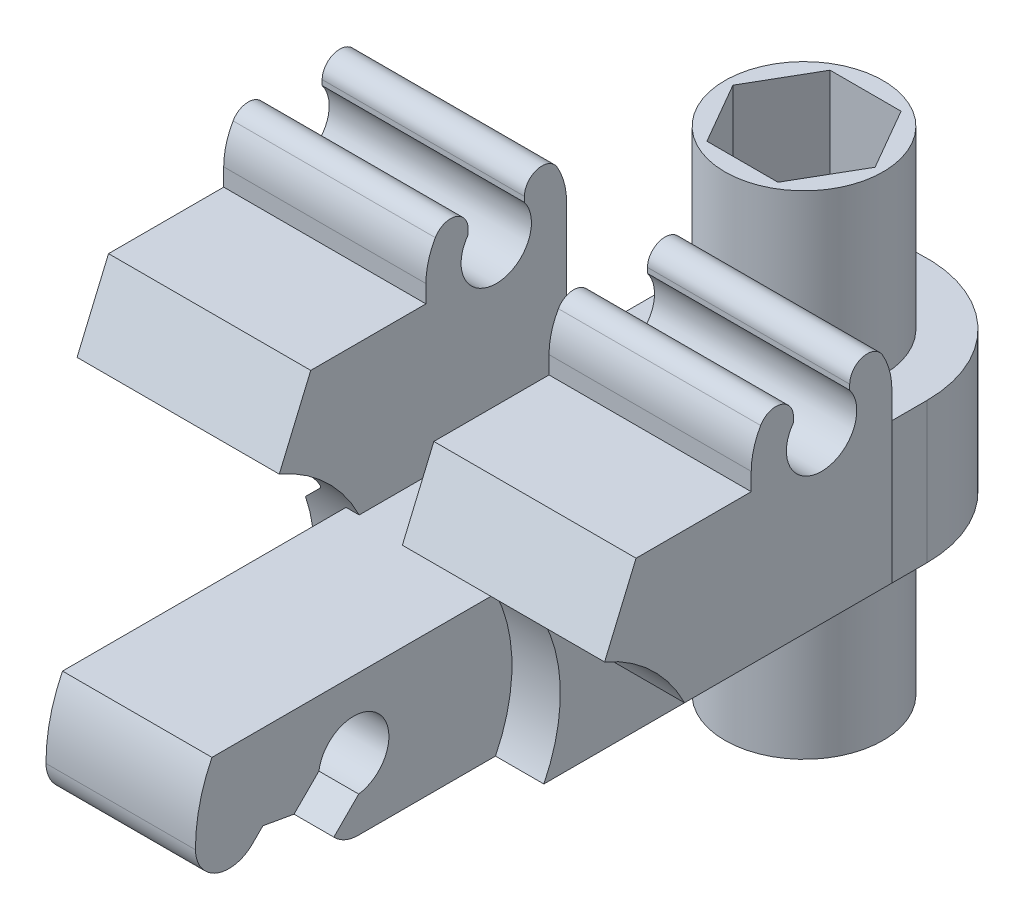
SolidWorks part; units mm, degrees
ref_plane "Front Plane" through (0, 0, 0) normal (0, 0, 1) x (1, 0, 0)
ref_plane "Top Plane" through (0, 0, 0) normal (0, 1, 0) x (1, 0, 0)
ref_plane "Right Plane" through (0, 0, 0) normal (1, 0, 0) x (0, 0, -1)
sketch "Sketch3" plane through (0, 0, 0) normal (1, 0, 0) x (0, 0, -1)
  line L0 (0.2828, -1.9799) -> (-1.9799, 0.2828)
  line L1 (0.2828, -1.9799) -> (-1.1314, -3.3941)
  line L2 (-1.1314, -3.3941) -> (-0.8188, -5.1668)
  line L3 (-0.8188, -5.1668) -> (-3.8071, -8.1551)
  line L4 (-1.9799, 0.2828) -> (-3.3941, -1.1314)
  line L5 (-3.3941, -1.1314) -> (-5.1668, -0.8188)
  line L6 (-5.1668, -0.8188) -> (-8.1551, -3.8071)
  line L7 (-0.8485, -0.8485) -> (0, 0) construction
  line L8 (0, 0) -> (-2, 0) construction
  line L9 (-1.9799, 0.2828) -> (-5.1668, -0.8188) construction
  line L10 (-0.8188, -5.1668) -> (0.2828, -1.9799) construction
  circle A0 centre (0, 0) radius 2
  circle A1 centre (0, 0) radius 8.5 construction
  circle A2 centre (0, 0) radius 9 construction
  circle A3 centre (0, 0) radius 9
  dimension "D1" = 4
  dimension "D2" = 17
  dimension "D3" = 7
  dimension "D4" = 0.5
  dimension "D5" = 2
  dimension "D7" = 3.2
  dimension "D6" = 1.8
  dimension "D8" = 45
  dimension "D9" = 125
extrude "Boss-Extrude1" add sketch "Sketch3" along normal mid plane 8.5 contours A3 L6 L5 L4 A0 L1 L2 L3 | A3 region at (0, -1.4772, -1.7032)
sketch "Sketch5" plane through (0, 0, 0) normal (1, 0, 0) x (0, 0, -1)
  line L0 (0, 9) -> (29.856, 9)
  line L1 (29.856, 9) -> (29.856, -9)
  line L2 (29.856, -9) -> (0, -9)
  arc A0 (-3.8071, -8.1551) -> (-8.1551, -3.8071) centre (0, 0) ccw construction
  arc A1 (0, -9) -> (0, 9) centre (0, 0) ccw
  dimension "D1" = 29.856
extrude "Boss-Extrude2" add sketch "Sketch5" along normal mid plane 14
sketch "Sketch6" plane through (0, 9, 0) normal (0, 1, 0) x (1, 0, 0)
  line L0 (7, 29.856) -> (-7, 29.856) construction
  circle A0 centre (0, 29.856) radius 7
extrude "Boss-Extrude3" add sketch "Sketch6" against normal up to surface (18 mm away) up to face at (0, -9, -9.952)
sketch "Sketch7" plane through (0, 0, 0) normal (0, 1, 0) x (1, 0, 0)
  circle A0 centre (0, 29.856) radius 4.5
  dimension "D1" = 9
extrude "Boss-Extrude4" add sketch "Sketch7" along normal blind 14 and the other way blind 14
sketch "Sketch22" plane through (0, 14, 0) normal (0, 1, 0) x (1, 0, 0)
  circle A0 centre (0, 29.856) radius 3
  dimension "D1" = 6
extrude "Boss-Extrude6" [suppressed] add sketch "Sketch22" along normal blind 18
sketch "Sketch8" plane through (0, 9, 0) normal (0, 1, 0) x (1, 0, 0)
  line L0 (4.25, -9) -> (4.25, 0) construction
  line L1 (-4.25, 0) -> (-4.25, -9) construction
  line L3 (7, 0) -> (7, 29.856) construction
  line L4 (-7, 29.856) -> (-7, 0) construction
  line L5 (-7, 0) -> (-4.25, 0) construction
  line L6 (4.25, 0) -> (7, 0) construction
  line L7 (4.25, -9) -> (4.25, 0)
  line L8 (-4.25, 0) -> (-4.25, -9)
  line L9 (-4.25, -9) -> (4.25, -9)
  line L10 (7, 0) -> (7, 29.856)
  line L11 (-7, 29.856) -> (-7, 0)
  line L12 (-7, 0) -> (-4.25, 0)
  line L13 (4.25, 0) -> (7, 0)
  arc A0 (7, 29.856) -> (-7, 29.856) centre (0, 29.856) ccw construction
  arc A1 (7, 29.856) -> (-7, 29.856) centre (0, 29.856) ccw
  circle M9 centre (0, 29.856) radius 4.5
  line M10 (7, 0) -> (7, 29.856)
  arc M11 (7, 29.856) -> (-7, 29.856) centre (0, 29.856) ccw
  line M12 (-7, 29.856) -> (-7, 0)
  line M13 (-7, 0) -> (-4.25, 0)
  line M14 (-4.25, 0) -> (4.25, 0)
  line M15 (4.25, 0) -> (7, 0)
extrude "Cut-Extrude2" cut sketch "Sketch8" against normal offset from surface (5 mm away) 4 contours M15 M10 M11 M12 M13 M14 M9 | L8 L9 L7 M14 region at (0, 9, 4.5) region at (0, 9, -15.9202) up to plane "Top Plane"
sketch "Sketch9" plane through (0, -9, 0) normal (0, -1, 0) x (1, 0, 0)
  line L7 (4.25, 0) -> (4.25, 9)
  line L8 (7, 0) -> (4.25, 0)
  line L9 (7, -29.856) -> (7, 0)
  line L10 (-7, 0) -> (-7, -29.856)
  line L11 (-4.25, 0) -> (-7, 0)
  line L12 (-4.25, 9) -> (-4.25, 0)
  line L13 (4.25, 9) -> (-4.25, 9)
  line L14 (4.25, 0) -> (4.25, 9)
  line L15 (7, 0) -> (4.25, 0)
  line L16 (7, -29.856) -> (7, 0)
  line L17 (-7, 0) -> (-7, -29.856)
  line L18 (-4.25, 0) -> (-7, 0)
  line L19 (-4.25, 9) -> (-4.25, 0)
  line L20 (4.25, 9) -> (-4.25, 9)
  arc A1 (-7, -29.856) -> (7, -29.856) centre (0, -29.856) ccw
  arc A2 (-7, -29.856) -> (7, -29.856) centre (0, -29.856) ccw
  circle M9 centre (0, -29.856) radius 4.5
  line M10 (-7, 0) -> (-7, -29.856)
  arc M11 (-7, -29.856) -> (7, -29.856) centre (0, -29.856) ccw
  line M12 (7, -29.856) -> (7, 0)
  line M13 (7, 0) -> (4.25, 0)
  line M14 (4.25, 0) -> (-4.25, 0)
  line M15 (-4.25, 0) -> (-7, 0)
  dimension "D1" = 0
extrude "Cut-Extrude4" cut sketch "Sketch9" against normal offset from surface (5 mm away) 4 contours M15 M10 M11 M12 M13 M14 M9 | L14 L20 L19 M14 region at (0, -9, 4.5) region at (0, -9, -15.9202) up to plane "Top Plane"
sketch "Sketch10" plane through (0, 0, 0) normal (1, 0, 0) x (0, 0, -1)
  line L3 (8.0623, -4) -> (29.856, -4)
  line L4 (29.856, -4) -> (29.856, 4)
  line L5 (29.856, 4) -> (8.0623, 4)
  line L10 (11.856, 12.5) -> (11.856, 17.5) construction
  line L11 (11.856, 17.5) -> (19.856, 17.5) construction
  line L12 (19.856, 17.5) -> (19.856, 4) construction
  line L13 (5.3059, 12.5) -> (11.856, 12.5)
  line L14 (0, 0) -> (3.5166, 8.2845) construction
  line L15 (3.5166, 8.2845) -> (5.3059, 12.5)
  line L16 (29.856, 4) -> (8.0623, 4) construction
  line L17 (19.856, 4) -> (8.0623, 4)
  line L18 (11.856, 13.5) -> (19.856, 13.5) construction
  line L19 (29.856, 14) -> (29.856, 4) construction
  line L20 (34.356, 14) -> (25.356, 14) construction
  line L21 (14.256, 14.7) -> (17.456, 14.7) construction
  line L22 (17.456, 14.7) -> (17.456, 17.1661)
  line L23 (14.256, 17.1661) -> (14.256, 14.7)
  line L24 (11.856, 13.5) -> (11.856, 12.5)
  line L25 (19.856, 13.5) -> (19.856, 4)
  arc A0 (14.256, 14.7) -> (17.456, 14.7) centre (15.856, 13.5) ccw
  arc A1 (8.0623, -4) -> (8.0623, 4) centre (0, 0) ccw
  arc A2 (8.0623, 4) -> (3.5166, 8.2845) centre (0, 0) ccw
  arc A3 (19.856, 13.5) -> (17.456, 17.1661) centre (15.856, 13.5) ccw
  arc A4 (14.256, 17.1661) -> (11.856, 13.5) centre (15.856, 13.5) ccw
  dimension "D8" = 4
  dimension "D9" = 2
  dimension "D10" = 3.2
  dimension "D2" = 67
  dimension "D3" = 10
  dimension "D4" = 13.5
  dimension "D5" = 5
  dimension "D7" = 5
  dimension "D1" = 0
extrude "Boss-Extrude5" add sketch "Sketch10" along normal mid plane 30
ref_plane "Plane1" through (6, 0, 0) normal (1, 0, 0) x (0, 0, -1)
ref_plane "Plane2" through (-6, 0, 0) normal (1, 0, 0) x (0, 0, -1)
sketch "Sketch13" plane through (-6, 0, 0) normal (1, 0, 0) x (0, 0, -1)
  line L0 (0, 5) -> (34.356, 5)
  line L1 (34.356, 4) -> (34.356, 14) construction
  circle A0 centre (0, 0) radius 5 construction
  dimension "D1" = 10
ref_plane "Plane3" through (0, 0, 0) normal (0, 0, 1) x (1, 0, 0)
sketch "Sketch14" plane through (0, 0, 0) normal (0, 0, 1) x (1, 0, 0)
  line L0 (-6.5303, 5.5303) -> (-8.0607, 4)
  line L1 (-7, 4) -> (-15, 4) construction
  line L2 (-5.4697, 4.4697) -> (-7, 2.9393)
  line L3 (-7, 4) -> (-7, -4) construction
  line L4 (-6.5303, 5.5303) -> (-5.4697, 4.4697) construction
  line L5 (-8.0607, 4) -> (-7, 4)
  line L6 (-7, 4) -> (-7, 2.9393)
  arc A0 (-5.4697, 4.4697) -> (-6.5303, 5.5303) centre (-6, 5) ccw
  point P14 (-6, 5)
  dimension "D1" = 1.5
  dimension "D2" = 45
sweep "Cut-Sweep1" cut profiles "Sketch14" path "Sketch13"
ref_plane "Plane4" [suppressed] through (0, 0, -32.856) normal (0, 0, -1) x (-1, 0, 0)
ref_plane "Plane5" [suppressed] through (-3, 0, 0) normal (-1, 0, 0) x (0, 0, 1)
sketch "Sketch18" [suppressed] plane through (0, 0, -32.856) normal (0, 0, -1) x (-1, 0, 0)
  line L0 (0, 29) -> (0, 16) construction
  line L2 (3, 29) -> (-3, 29) construction
  circle A0 centre (0, 16) radius 1.9
  dimension "D2" = 3.8
  dimension "D1" = 13
extrude "Cut-Extrude5" [suppressed] cut sketch "Sketch18" against normal blind 1
sketch "Sketch20" plane through (0, 14, 0) normal (0, 1, 0) x (1, 0, 0)
  line L0 (0, 25.356) -> (0, 0) construction
  line L2 (-3.5, -19.856) -> (3.5, -19.856)
  line L3 (-3.5, -19.856) -> (-3.5, 19.856)
  line L4 (-3.5, 19.856) -> (3.5, 19.856)
  line L5 (3.5, -19.856) -> (3.5, 19.856)
  line L6 (-3.5, -19.856) -> (3.5, 19.856) construction
  line L7 (-3.5, 19.856) -> (3.5, -19.856) construction
  line L8 (-5.9393, 19.856) -> (7, 19.856) construction
  circle A0 centre (0, 29.856) radius 4.5 construction
  circle A1 centre (0, 29.856) radius 4.5 construction
  dimension "D1" = 7
extrude "Cut-Extrude7" cut sketch "Sketch20" against normal up to surface (10 mm away) and the other way through all up to face at (0, 4, 0)
fillet "Fillet1" radius 1.9 2 edges at (0, -3.8071, 8.1551) (0, -4, 1.0245)
fillet "Fillet2" radius 1 4 edges at (-9.25, 17.1661, -17.456) (-9.25, 17.1661, -14.256) (9.25, 17.1661, -14.256) (9.25, 17.1661, -17.456)
sketch "Sketch23" plane through (0, 14, 0) normal (0, 1, 0) x (1, 0, 0)
  line L1 (4.0415, 29.856) -> (2.0207, 33.356)
  line L2 (2.0207, 33.356) -> (-2.0207, 33.356)
  line L3 (-2.0207, 33.356) -> (-4.0415, 29.856)
  line L4 (-4.0415, 29.856) -> (-2.0207, 26.356)
  line L5 (-2.0207, 26.356) -> (2.0207, 26.356)
  line L6 (2.0207, 26.356) -> (4.0415, 29.856)
  circle A0 centre (0, 29.856) radius 3.5 construction
  point P1 (4.0415, 29.856)
  dimension "D1" = 7
extrude "Cut-Extrude8" cut sketch "Sketch23" against normal through all
